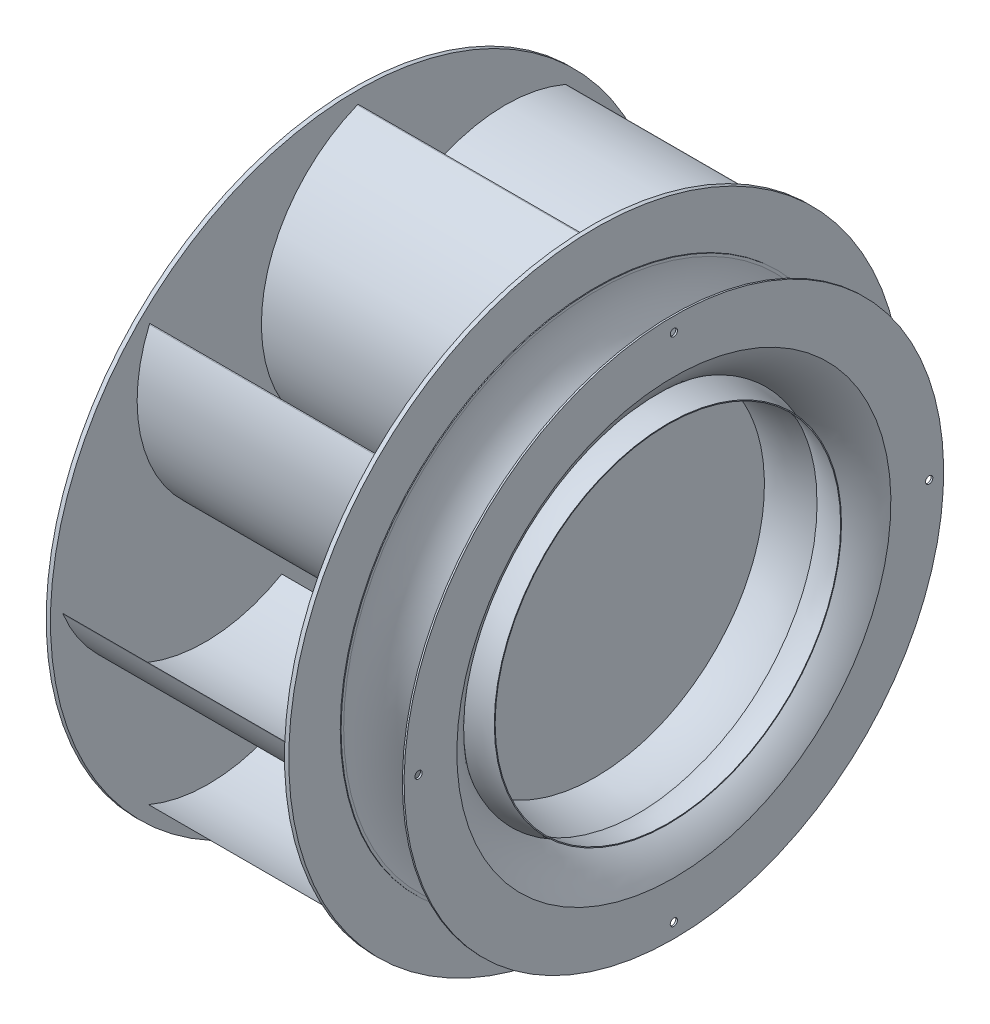
SolidWorks part; units mm, degrees
ref_plane "Front Plane" through (0, 0, 0) normal (0, 0, 1) x (1, 0, 0)
ref_plane "Top Plane" through (0, 0, 0) normal (0, 1, 0) x (1, 0, 0)
ref_plane "Right Plane" through (0, 0, 0) normal (1, 0, 0) x (0, 0, -1)
sketch "Sketch1" plane through (0, 0, 0) normal (0, 0, 1) x (1, 0, 0)
  line L0 (0, 0) -> (831.9083, 0) construction
  line L1 (0, 0) -> (0, 109)
  line L2 (5, 114) -> (70, 114)
  line L3 (70, 114) -> (70, 138)
  line L4 (70, 138) -> (90, 138)
  line L5 (90, 138) -> (90, 98)
  line L6 (90, 98) -> (92, 98)
  line L7 (92, 98) -> (92, 133)
  line L8 (92, 133) -> (95, 133)
  line L9 (95, 133) -> (95, 98)
  line L10 (95, 98) -> (97, 98)
  line L11 (97, 98) -> (97, 0)
  line L12 (97, 0) -> (0, 0)
  arc A0 (5, 114) -> (0, 109) centre (5, 109) ccw
  point P16 (0, 114)
  dimension "D10" = 5
  dimension "D1" = 114
  dimension "D2" = 24
  dimension "D3" = 70
  dimension "D4" = 40
  dimension "D5" = 35
  dimension "D6" = 2
  dimension "D7" = 20
  dimension "D8" = 3
  dimension "D9" = 27
revolve "Revolve1" add sketch "Sketch1" angle 360 about L0
sketch "Sketch2" plane through (97, 0, 0) normal (1, 0, 0) x (0, 0, -1)
  circle A0 centre (0, 0) radius 360.5
  dimension "D1" = 721
extrude "Extrude1" add sketch "Sketch2" along normal blind 5
sketch "Sketch9" plane through (97, 0, 0) normal (-1, 0, 0) x (0, 0, 1)
  circle A0 centre (0, 0) radius 355.5
  circle A1 centre (0, 0) radius 100
  circle A2 centre (0, 0) radius 360.5 construction
  dimension "D1" = 5
  dimension "D2" = 200
extrude "Extrude7" cut sketch "Sketch9" against normal blind 3
ref_plane "Plane1" through (377, 0, 0) normal (1, 0, 0) x (0, 0, -1)
sketch "Sketch3" plane through (377, 0, 0) normal (1, 0, 0) x (0, 0, -1)
  circle A0 centre (0, 0) radius 360.5
  dimension "D1" = 721
extrude "Extrude2" add sketch "Sketch3" along normal blind 5 separate body
sketch "Sketch4" plane through (102, 0, 0) normal (1, 0, 0) x (0, 0, -1)
  line L0 (0, 0) -> (0, 345.5) construction
  line L1 (0, 0) -> (254.912, 254.912) construction
  line L2 (0, 125) -> (0.866, 124.5)
  line L3 (244.3054, 244.3054) -> (245.1714, 243.8054)
  circle A0 centre (0, 0) radius 345.5 construction
  circle A1 centre (0, 0) radius 360.5 construction
  circle A2 centre (0, 0) radius 125 construction
  arc A3 (0, 125) -> (244.3054, 244.3054) centre (173.926, 78.6348) cw
  arc A4 (0.866, 124.5) -> (245.1714, 243.8054) centre (174.7921, 78.1348) cw
  dimension "D1" = 15
  dimension "D2" = 250
  dimension "D6" = 180
  dimension "D7" = 180
  dimension "D3" = 45
  dimension "D4" = 60
  dimension "D5" = 1
extrude "Extrude3" add sketch "Sketch4" along normal up to surface (280 mm away) up to face at (382, 0, -360.5)
ref_axis "Axis1" through (253.5503, 0, 0) along (-1, 0, 0)
pattern_circular "CirPattern1" count 8 over 360 about axis through (253.5503, 0, 0) along (-1, 0, 0) of "Extrude3"
sketch "Sketch5" plane through (0, 0, 0) normal (0, 0, 1) x (1, 0, 0)
  line L0 (0, 0) -> (527.2916, 0) construction
  line L1 (253.5503, 0) -> (75.411, 0) construction
  line L2 (382, 300) -> (383, 300)
  line L3 (383, 300) -> (383, 297)
  line L4 (382, 300) -> (382, 297)
  line L5 (467, 204) -> (467, 203)
  line L6 (70, 138) -> (70, -138) construction
  line L7 (382, -360.5) -> (382, 360.5) construction
  arc A0 (383, 297) -> (467, 204) centre (467.6225, 288.9977) ccw
  arc A1 (382, 297) -> (467, 203) centre (466.522, 287.9987) ccw
  dimension "D7" = 85
  dimension "D8" = 85
  dimension "D1" = 203
  dimension "D2" = 1
  dimension "D3" = 1
  dimension "D4" = 3
  dimension "D5" = 300
  dimension "D6" = 397
revolve "Revolve2" add sketch "Sketch5" angle 360 about L0
ref_plane "Plane3" through (474, 0, 0) normal (1, 0, 0) x (0, 0, -1)
sketch "Sketch6" plane through (0, 0, 0) normal (0, 0, 1) x (1, 0, 0)
  line L0 (474, 317) -> (472, 317)
  line L1 (474, -251.35) -> (474, 251.35) construction
  line L2 (472, 317) -> (472, 255)
  line L3 (0, 0) -> (615.1417, 0) construction
  line L4 (0, 114) -> (0, -114) construction
  line L5 (253.5503, 0) -> (75.411, 0) construction
  line L6 (474, 317) -> (474, 255)
  line L7 (357, 203) -> (361, 203)
  line L8 (357, 203) -> (357, 201)
  line L9 (357, 201) -> (361, 201)
  arc A0 (361, 203) -> (472, 255) centre (382.9789, 300.5548) ccw
  arc A1 (361, 201) -> (474, 255) centre (383.883, 298.3466) ccw
  dimension "D7" = 100
  dimension "D8" = 100
  dimension "D1" = 317
  dimension "D2" = 2
  dimension "D3" = 255
  dimension "D4" = 117
  dimension "D5" = 203
  dimension "D6" = 4
revolve "Revolve3" add sketch "Sketch6" angle 360 about L3
sketch "Sketch7" plane through (474, 0, 0) normal (1, 0, 0) x (0, 0, -1)
  line L0 (0, 0) -> (0, 300) construction
  circle A0 centre (0, 0) radius 300 construction
  circle A1 centre (0, 300) radius 4.25
  dimension "D1" = 600
  dimension "D2" = 8.5
extrude "Extrude5" cut sketch "Sketch7" against normal blind 5
pattern_circular "CirPattern2" count 4 over 360 about axis through (253.5503, 0, 0) along (-1, 0, 0) of "Extrude5"
sketch "Sketch8" plane through (0, 0, 0) normal (1, 0, 0) x (0, 0, -1)
  line L0 (0, 0) -> (0, 126) construction
  circle A0 centre (0, 0) radius 126 construction
  circle A1 centre (0, 126) radius 5
  dimension "D1" = 252
  dimension "D2" = 10
extrude "Extrude6" cut sketch "Sketch8" along normal up to surface (90 mm away) up to face at (90, 0, 138)
pattern_circular "CirPattern3" count 8 over 360 about axis through (253.5503, 0, 0) along (-1, 0, 0) of "Extrude6"
